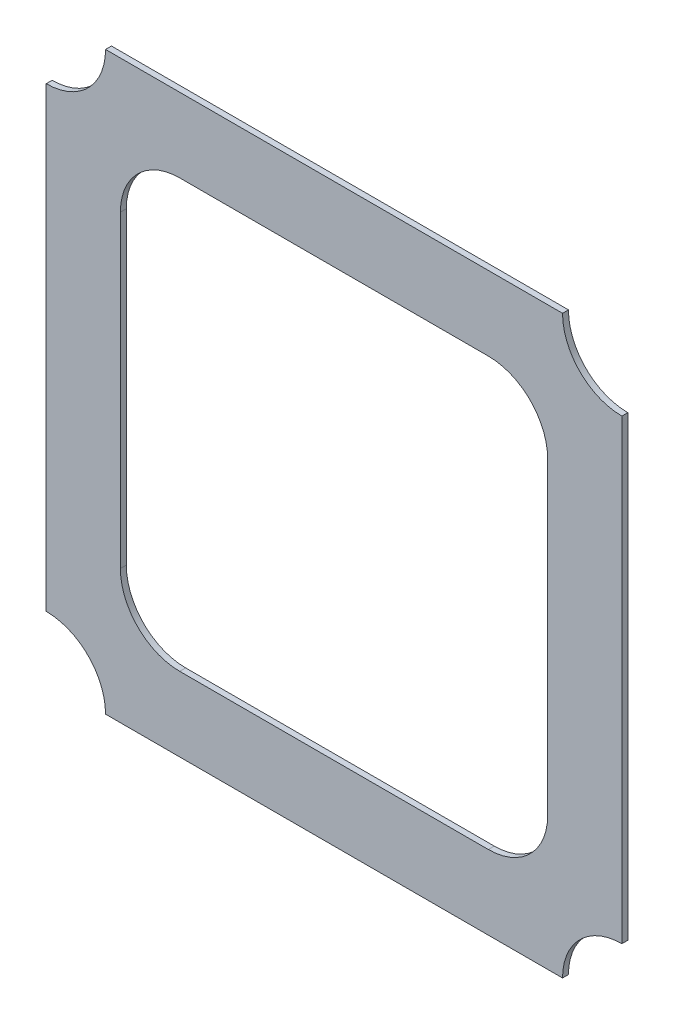
SolidWorks part; units mm, degrees
material "7075-T6, Plate (SS)"
ref_plane "Front Plane" through (0, 0, 0) normal (0, 0, 1) x (1, 0, 0)
ref_plane "Top Plane" through (0, 0, 0) normal (0, 1, 0) x (1, 0, 0)
ref_plane "Right Plane" through (0, 0, 0) normal (1, 0, 0) x (0, 0, -1)
sketch "Sketch1" plane through (0, 0, 0) normal (0, 0, 1) x (1, 0, 0)
  line L1 (-48.5, 48.5) -> (48.5, 48.5)
  line L2 (-48.5, 48.5) -> (-48.5, -48.5)
  line L3 (-48.5, -48.5) -> (48.5, -48.5)
  line L4 (48.5, 48.5) -> (48.5, -48.5)
  line L5 (-36, 36) -> (36, 36)
  line L6 (-36, 36) -> (-36, -36)
  line L7 (-48.5, 48.5) -> (-27.8298, 48.5)
  line L8 (-48.5, 48.5) -> (-48.5, 27.8298)
  line L11 (48.5, 48.5) -> (28.5862, 48.5)
  line L12 (48.5, 48.5) -> (48.5, 28.5862)
  line L15 (48.5, -48.5) -> (28.5862, -48.5)
  line L16 (48.5, -48.5) -> (48.5, -28.5862)
  line L19 (-48.5, -48.5) -> (-27.8298, -48.5)
  line L20 (-48.5, -48.5) -> (-48.5, -27.8298)
  line L23 (-36, -36) -> (36, -36)
  line L24 (36, 36) -> (36, -36)
  line L25 (-36, 36) -> (36, -36) construction
  line L26 (-36, -36) -> (36, 36) construction
  point P0 (0, 0)
  point P6 (0, 0)
  dimension "D1" = 97
  dimension "D2" = 97
  dimension "D3" = 12.5
  dimension "D4" = 12.5
  dimension "D5" = 12.5
  dimension "D6" = 12.5
extrude "Boss-Extrude1" add sketch "Sketch1" along normal blind 1 contours L4 L1 L2 L3 L5 L24 L23 L6 region at (-38.1649, 47.1282, 0)
sketch "Sketch2" plane through (0, 0, 1) normal (0, 0, 1) x (1, 0, 0)
  line L1 (-48.5, 48.5) -> (-38.5, 48.5)
  line L2 (-48.5, 48.5) -> (-48.5, 38.5)
  line L3 (-48.5, 38.5) -> (-38.5, 38.5)
  line L4 (-38.5, 48.5) -> (-38.5, 38.5)
  line L5 (48.5, 48.5) -> (38.5, 48.5)
  line L6 (48.5, 48.5) -> (48.5, 38.5)
  line L7 (48.5, 38.5) -> (38.5, 38.5)
  line L8 (38.5, 48.5) -> (38.5, 38.5)
  line L9 (48.5, -48.5) -> (38.5, -48.5)
  line L10 (48.5, -48.5) -> (48.5, -38.5)
  line L11 (48.5, -38.5) -> (38.5, -38.5)
  line L12 (38.5, -48.5) -> (38.5, -38.5)
  line L13 (-48.5, -48.5) -> (-38.5, -48.5)
  line L14 (-48.5, -48.5) -> (-48.5, -38.5)
  line L15 (-48.5, -38.5) -> (-38.5, -38.5)
  line L16 (-38.5, -48.5) -> (-38.5, -38.5)
  dimension "D1" = 10
  dimension "D2" = 10
  dimension "D3" = 10
  dimension "D4" = 10
  dimension "D5" = 10
  dimension "D6" = 10
  dimension "D7" = 10
  dimension "D8" = 10
extrude "Cut-Extrude1" cut sketch "Sketch2" against normal through all contours L2 L1 L4 L3 | L6 L5 L8 L7 | L10 L9 L12 L11 | L14 L13 L16 L15
fillet "Fillet1" radius 10 8 edges at (-36, -36, 0.5) (-38.5, -38.5, 0.5) (38.5, -38.5, 0.5) (36, -36, 0.5) (38.5, 38.5, 0.5) (36, 36, 0.5) (-38.5, 38.5, 0.5) (-36, 36, 0.5)
